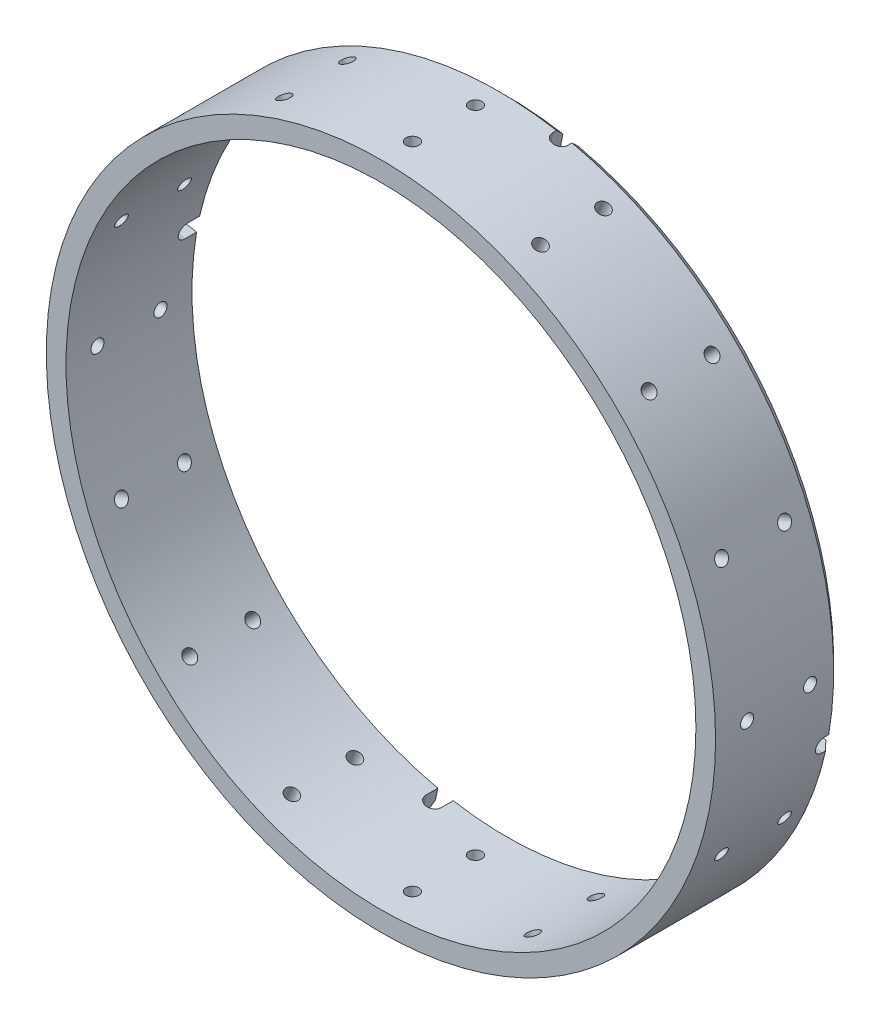
SolidWorks part; units mm, degrees
material "6063-T6"
ref_plane "Płaszczyzna przednia" through (0, 0, 0) normal (0, 0, 1) x (1, 0, 0)
ref_plane "Płaszczyzna górna" through (0, 0, 0) normal (0, 1, 0) x (1, 0, 0)
ref_plane "Płaszczyzna prawa" through (0, 0, 0) normal (1, 0, 0) x (0, 0, -1)
sketch "Szkic1" plane through (0, 0, 0) normal (0, 0, 1) x (1, 0, 0)
  circle A0 centre (0, 0) radius 85
  circle A1 centre (0, 0) radius 80
  dimension "D1" = 170
  dimension "D2" = 5
extrude "Dodanie-wyciągnięcie1" add sketch "Szkic1" along normal blind 32
sketch "Szkic2" plane through (0, 0, 32) normal (0, 0, 1) x (1, 0, 0)
  line L0 (0, 46.3429) -> (0, 98.4468) construction
  circle A0 centre (0, 0) radius 85 construction
  circle A1 centre (0, 0) radius 85
  point P6 (0, 85)
sketch3d "Szkic 3D1"
sketch "Szkic3" plane through (0, 85, 0) normal (0, 1, 0) x (1, 0, 0)
  line L0 (0, 18.1334) -> (0, -45.2976) construction
  line L1 (80, 0) -> (-80, 0) construction
  circle A0 centre (0, -8) radius 1.65
  circle A1 centre (0, -24) radius 1.65
  dimension "D1" = 3.3
  dimension "D2" = 3.3
  dimension "D3" = 8
  dimension "D4" = 16
extrude "Wytnij-wyciągnięcie1" cut sketch "Szkic3" against normal blind 32
pattern_circular "Szyk kołowy1" count 16 over 360 about axis through (0, 0, 32) along (0, 0, -1) of "Wytnij-wyciągnięcie1"
chamfer "Sfazowanie1" distance 2 angle 45 1 edges at (85, 0, 0)
sketch "Szkic5" plane through (0, 0, 0) normal (0, 0, -1) x (-1, 0, 0)
  line L0 (0, 109.5264) -> (0, 0) construction
  line L1 (-23.4011, 117.6453) -> (0, 0) construction
  line L2 (-18.5397, 82.9535) -> (-17.5639, 78.0481)
  line L3 (-14.6165, 83.7338) -> (-13.6408, 78.8285)
  line L5 (-21.4395, 118.0355) -> (1.9616, 0.3902) construction
  line L6 (-25.3627, 117.2552) -> (-1.9616, -0.3902) construction
  circle A0 centre (0, 0) radius 85 construction
  circle A1 centre (0, 0) radius 80 construction
  arc A2 (-14.6165, 83.7338) -> (-18.5397, 82.9535) centre (0, 0) ccw
  arc A3 (-13.6408, 78.8285) -> (-17.5639, 78.0481) centre (0, 0) ccw
  dimension "D1" = 11.25
  dimension "D2" = 2
  dimension "D3" = 2
extrude "Wytnij-wyciągnięcie2" cut sketch "Szkic5" against normal blind 5
fillet "Zaokrąglenie2" radius 2 2 edges at (14.1286, 81.2812, 5) (18.0518, 80.5008, 5)
pattern_circular "Szyk kołowy4" count 4 over 360 about axis through (0, 0, 0) along (0, 0, 1) of "Zaokrąglenie2", "Wytnij-wyciągnięcie2"
